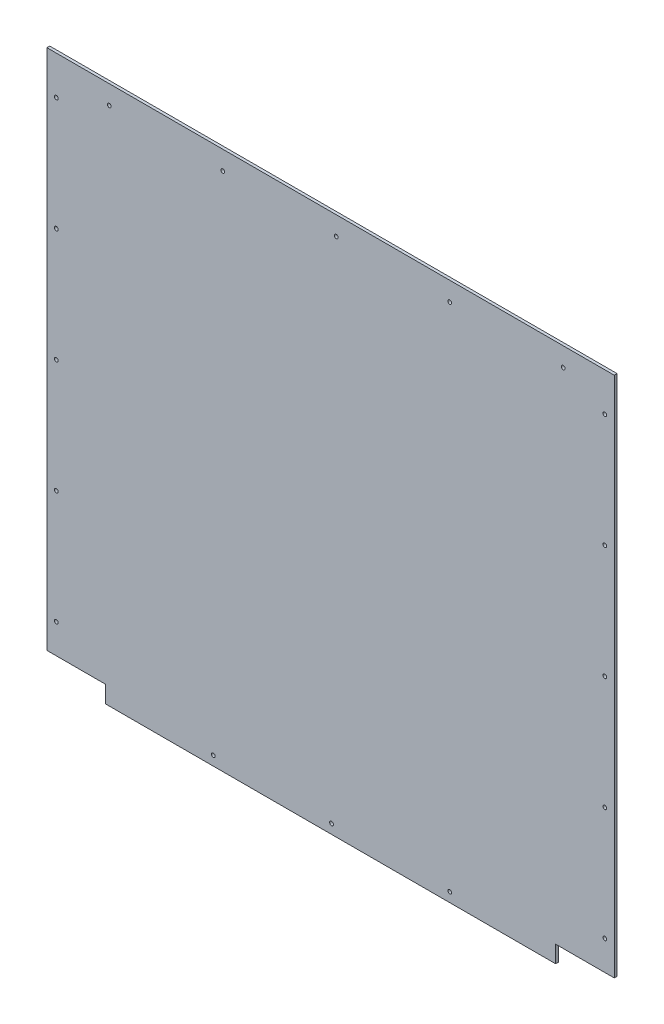
SolidWorks part; units mm, degrees
ref_plane "Płaszczyzna przednia" through (0, 0, 0) normal (0, 0, 1) x (1, 0, 0)
ref_plane "Płaszczyzna górna" through (0, 0, 0) normal (0, 1, 0) x (1, 0, 0)
ref_plane "Płaszczyzna prawa" through (0, 0, 0) normal (1, 0, 0) x (0, 0, -1)
sketch "Sketch1" plane through (0, 0, 0) normal (0, 0, 1) x (1, 0, 0)
  line L1 (0, 0) -> (600, 0)
  line L2 (0, 0) -> (0, 570)
  line L3 (0, 570) -> (600, 570)
  line L4 (600, 0) -> (600, 570)
  line L5 (0, 0) -> (600, 570) construction
  line L6 (0, 570) -> (600, 0) construction
  point P4 (300, 285)
  dimension "D1" = 600
  dimension "D2" = 570
extrude "Boss-Extrude1" add sketch "Sketch1" along normal blind 3
sketch "Sketch2" plane through (0, 0, 3) normal (0, 0, 1) x (1, 0, 0)
  line L1 (0, 0) -> (62, 0)
  line L2 (0, 0) -> (0, 18)
  line L3 (0, 18) -> (62, 18)
  line L4 (62, 0) -> (62, 18)
  line L5 (0, 0) -> (62, 18) construction
  line L6 (0, 18) -> (62, 0) construction
  line L7 (600, 0) -> (538, 0)
  line L8 (600, 0) -> (600, 18)
  line L9 (600, 18) -> (538, 18)
  line L10 (538, 0) -> (538, 18)
  line L11 (600, 0) -> (538, 18) construction
  line L12 (600, 18) -> (538, 0) construction
  point P4 (31, 9)
  point P10 (569, 9)
  dimension "D1" = 62
  dimension "D2" = 18
  dimension "D3" = 18
  dimension "D4" = 62
extrude "Cut-Extrude1" cut sketch "Sketch2" against normal blind 3
hole_wizard "Ø4.0mm Dowel Hole1" positions "Sketch3" profile "Sketch4" hole size "Ø4.0" standard "ANSI Metric" end condition through all
sketch "Sketch3" plane through (0, 0, 0) normal (0, 0, -1) x (-1, 0, 0)
  line L0 (-600, 570) -> (0, 570) construction
  line L1 (-600, 18) -> (-600, 570) construction
  line L2 (-62, 0) -> (-538, 0) construction
  point P0 (-546, 550)
  point P2 (-590, 529.25)
  point P4 (-426, 10)
  point P17 (-426, 550)
  point P18 (-306, 550)
  point P19 (-186, 550)
  point P20 (-66, 550)
  point P34 (-10, 529.25)
  point P35 (-10, 409.25)
  point P36 (-10, 289.25)
  point P37 (-10, 169.25)
  point P38 (-10, 49.25)
  point P39 (-590, 409.25)
  point P40 (-590, 289.25)
  point P41 (-590, 169.25)
  point P42 (-590, 49.25)
  point P48 (-301, 10)
  point P49 (-176, 10)
  dimension "D1" = 20
  dimension "D2" = 54
  dimension "D3" = 10
  dimension "D4" = 40.75
  dimension "D5" = 10
  dimension "D9" = 0
  dimension "D6" = 5
  dimension "D7" = 2
  dimension "D8" = 5
  dimension "D10" = 3
sketch "Sketch4" plane through (546, 550, 0) normal (1, 0, 0) x (0, 1, 0)
  line L0 (0, 0) -> (0, 3)
  line L1 (0, 3) -> (2, 3)
  line L2 (2, 3) -> (2, 0)
  line L5 (2, 0) -> (0, 0)
  line L11 (0, -6.35) -> (0, 107.95) construction
  dimension "Thru Hole Dia." = 4
  dimension "Thru Hole Depth" = 3
